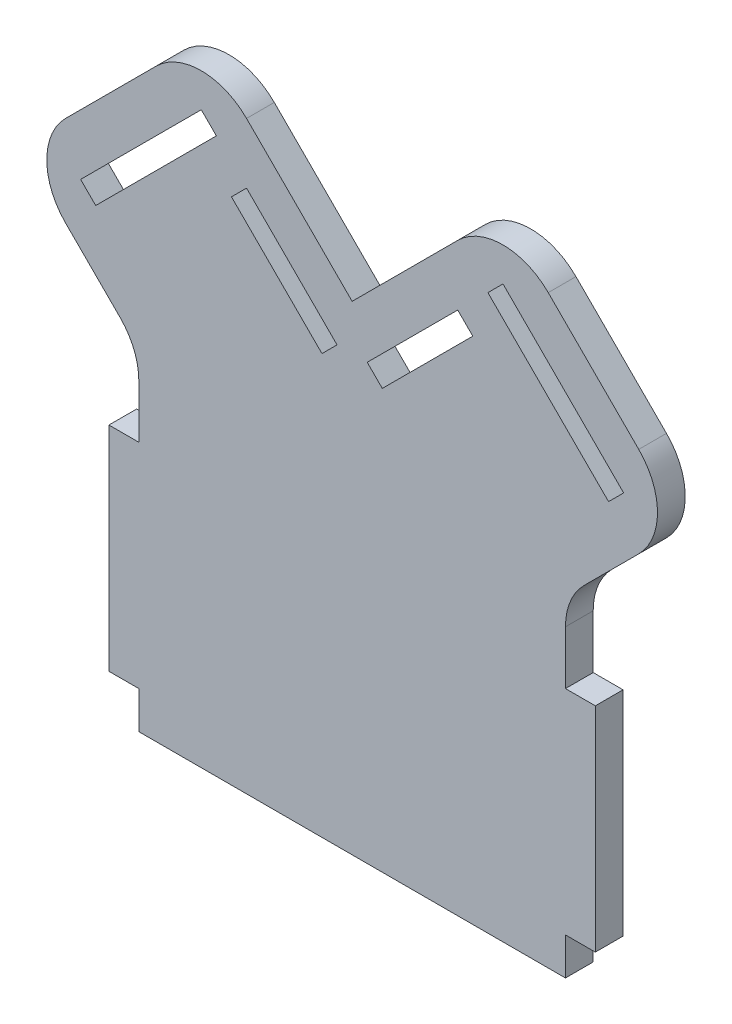
SolidWorks part; units mm, degrees
ref_plane "Front Plane" through (0, 0, 0) normal (0, 0, 1) x (1, 0, 0)
ref_plane "Top Plane" through (0, 0, 0) normal (0, 1, 0) x (1, 0, 0)
ref_plane "Right Plane" through (0, 0, 0) normal (1, 0, 0) x (0, 0, -1)
sketch "Sketch1" plane through (0, 0, 0) normal (0, 0, 1) x (1, 0, 0)
  line L0 (-10, 8.75) -> (-15.5563, 14.3063)
  line L1 (-10, 8.75) -> (10, 8.75)
  line L2 (-10, 8.75) -> (-10, -8.75)
  line L3 (-10, -8.75) -> (10, -8.75)
  line L4 (10, 8.75) -> (10, -8.75)
  line L5 (-10, 8.75) -> (10, -8.75) construction
  line L6 (-10, -8.75) -> (10, 8.75) construction
  line L7 (-15.5563, 14.3063) -> (-7.0711, 22.7916)
  line L8 (-7.0711, 22.7916) -> (0, 15.7206)
  line L9 (0, -55) -> (0, 55) construction
  line L10 (0, 15.7206) -> (7.0711, 22.7916)
  line L11 (7.0711, 22.7916) -> (15.5563, 14.3063)
  line L12 (15.5563, 14.3063) -> (10, 8.75)
  line L13 (-10, 8.75) -> (10, 8.75)
  point P0 (0, 0)
  dimension "D1" = 20
  dimension "D2" = 17.5
  dimension "D3" = 0
  dimension "D4" = 10
  dimension "D5" = 12
extrude "Boss-Extrude1" add sketch "Sketch1" along normal blind 1.3 contours L12 L11 L10 L8 L7 L0 L2 L1 L4 | L13 L2 L3 L4 | L2 L13 L4 L1 region at (0, 14.4487, 0) region at (0, 0, 0)
fillet "Fillet1" radius 3 6 edges at (-10, 8.75, 0.65) (10, 8.75, 0.65) (-15.5563, 14.3063, 0.65) (-7.0711, 22.7916, 0.65) (7.0711, 22.7916, 0.65) (15.5563, 14.3063, 0.65)
sketch "Sketch2" plane through (0, 0, 1.3) normal (0, 0, 1) x (1, 0, 0)
  line L0 (-10, 7.5074) -> (-10, -8.75) construction
  line L1 (-10, 5) -> (-11.4, 5)
  line L2 (-10, 5) -> (-10, -5)
  line L3 (-10, -5) -> (-11.4, -5)
  line L4 (-11.4, 5) -> (-11.4, -5)
  line L5 (10, 7.5074) -> (10, -8.75) construction
  line L6 (10, 5) -> (11.4, 5)
  line L7 (10, 5) -> (10, -5)
  line L8 (10, -5) -> (11.4, -5)
  line L9 (11.4, 5) -> (11.4, -5)
  line L11 (55, 0) -> (-55, 0) construction
  line L12 (7.0711, 19.9632) -> (12.7279, 14.3063)
  line L13 (12.7279, 14.3063) -> (12.0208, 13.5992)
  line L14 (12.0208, 13.5992) -> (6.364, 19.2561)
  line L15 (6.364, 19.2561) -> (7.0711, 19.9632)
  line L16 (9.1924, 20.6703) -> (13.435, 16.4277) construction
  line L17 (0, 15.7206) -> (4.9497, 20.6703) construction
  line L18 (0, -55) -> (0, 55) construction
  line L19 (-12.7279, 14.3063) -> (-12.0208, 13.5992)
  line L20 (-6.364, 19.2561) -> (-7.0711, 19.9632)
  line L21 (-7.0711, 19.9632) -> (-12.7279, 14.3063)
  line L22 (-12.0208, 13.5992) -> (-6.364, 19.2561)
  dimension "D1" = 1.4
  dimension "D2" = 1.4
  dimension "D3" = 10
  dimension "D4" = 10
  dimension "D5" = 5
  dimension "D6" = 5
  dimension "D7" = 1
  dimension "D8" = 8
  dimension "D9" = 2
  dimension "D10" = 2
extrude "Cut-Extrude1" cut sketch "Sketch2" against normal through all contours L22 L20 L21 L19 | L14 L15 L12 L13
extrude "Boss-Extrude2" add sketch "Sketch2<3>" against normal blind 1.3 contours L4 L3 L2 L1 | L9 L8 L7 L6
sketch "Sketch2<3>" plane through (0, 0, 1.3) normal (0, 0, 1) x (1, 0, 0) same geometry as "Sketch2"
sketch "Sketch3" plane through (0, 0, 1.3) normal (0, 0, 1) x (1, 0, 0)
  line L0 (10, -5) -> (10, -8.75) construction
  line L1 (-10, -8.75) -> (10, -8.75)
  line L2 (-10, -8.75) -> (-10, -6.75)
  line L3 (-10, -6.75) -> (10, -6.75)
  line L4 (10, -8.75) -> (10, -6.75)
  dimension "D1" = 2
extrude "Cut-Extrude2" cut sketch "Sketch3" against normal through all
sketch "Sketch4" plane through (0, 0, 1.3) normal (0, 0, 1) x (1, 0, 0)
  line L0 (-7.0711, 19.9632) -> (-4.9497, 17.8419) construction
  line L1 (-4.9497, 17.8419) -> (-0.7071, 13.5992)
  line L2 (-0.7071, 13.5992) -> (-1.4142, 12.8921)
  line L3 (-1.4142, 12.8921) -> (-5.6569, 17.1348)
  line L4 (-5.6569, 17.1348) -> (-4.9497, 17.8419)
  line L5 (-0.7071, 13.5992) -> (0, 12.8921) construction
  line L6 (0, -0.715) -> (0, 0.715) construction
  line L8 (1.4142, 12.8921) -> (5.6569, 17.1348)
  line L9 (0.7071, 13.5992) -> (1.4142, 12.8921)
  line L10 (4.9497, 17.8419) -> (0.7071, 13.5992)
  line L11 (5.6569, 17.1348) -> (4.9497, 17.8419)
  dimension "D1" = 1
  dimension "D2" = 6
  dimension "D3" = 3
  dimension "D4" = 6
extrude "Cut-Extrude3" cut sketch "Sketch4" against normal through all
sketch "Sketch5" plane through (0, 0, 1.3) normal (0, 0, 1) x (1, 0, 0)
  line L0 (7.0711, 19.9632) -> (-0.5714, 12.3207) construction
  line L1 (7.0711, 19.9632) -> (13.0154, 14.0188) construction
